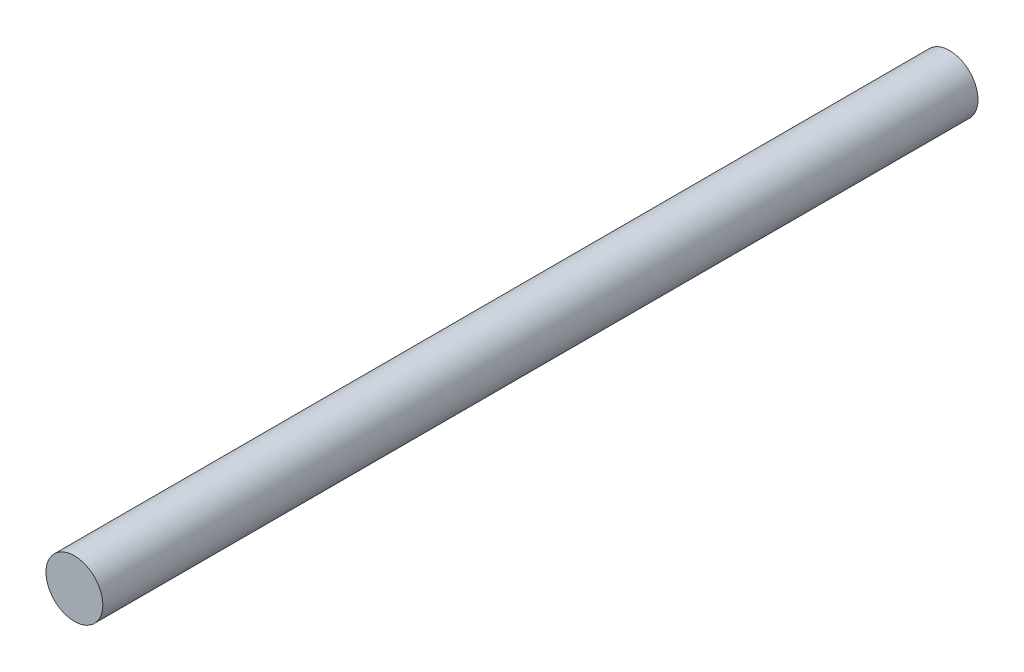
SolidWorks part; units mm, degrees
ref_plane "Front Plane" through (0, 0, 0) normal (0, 0, 1) x (1, 0, 0)
ref_plane "Top Plane" through (0, 0, 0) normal (0, 1, 0) x (1, 0, 0)
ref_plane "Right Plane" through (0, 0, 0) normal (1, 0, 0) x (0, 0, -1)
sketch "Sketch1" plane through (0, 0, 0) normal (0, 0, 1) x (1, 0, 0)
  circle A0 centre (0, 0) radius 1.95
  dimension "D1" = 3.9
extrude "Boss-Extrude1" add sketch "Sketch1" along normal blind 60
